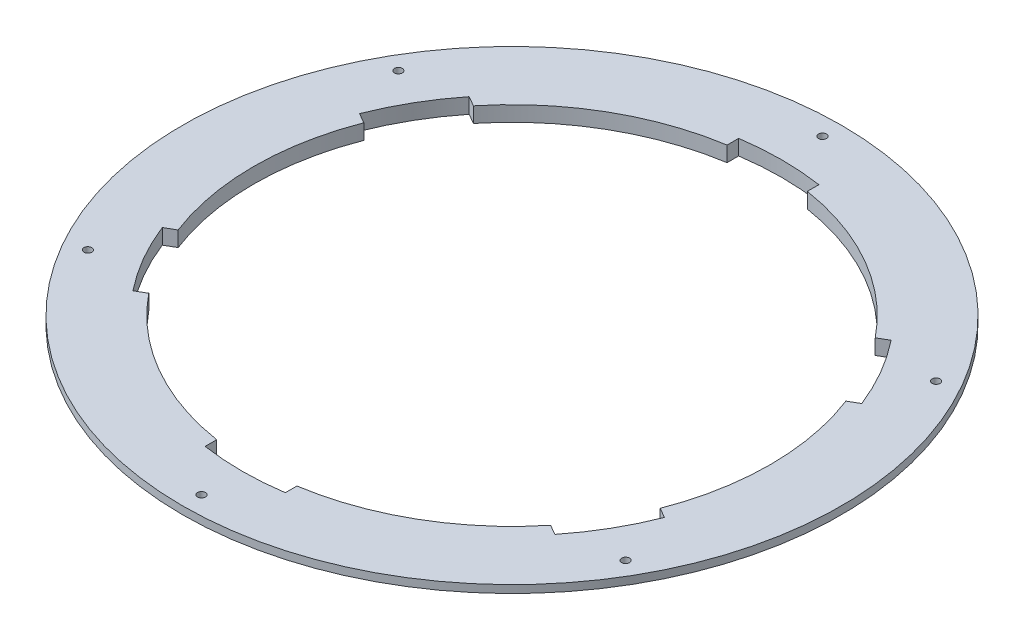
SolidWorks part; units mm, degrees
ref_plane "Front Plane" through (0, 0, 0) normal (0, 0, 1) x (1, 0, 0)
ref_plane "Top Plane" through (0, 0, 0) normal (0, 1, 0) x (1, 0, 0)
ref_plane "Right Plane" through (0, 0, 0) normal (1, 0, 0) x (0, 0, -1)
sketch "Sketch1" plane through (0, 0, 0) normal (0, 1, 0) x (1, 0, 0)
  line L0 (-13.335, -84.81) -> (-13.335, -88.6648)
  line L1 (13.335, -84.81) -> (13.335, -88.6648)
  circle A0 centre (0, 0) radius 85.852
  circle A1 centre (0, 0) radius 109.5375
  circle A2 centre (0, 0) radius 89.662
  circle A3 centre (0, -103.1875) radius 1.3208
  dimension "D1" = 171.704
  dimension "D2" = 219.075
  dimension "D8" = 2.6416
  dimension "D4" = 13.335
  dimension "D5" = 13.335
  dimension "D7" = 103.1875
  dimension "D3" = 3.81
extrude "Boss-Extrude1" add sketch "Sketch1" along normal blind 5.08 contours L1 A2 L0 A0 | A1 A2 A0 region at (-15.864, 0, 86.7374) region at (-106.4393, 0, 0)
pattern_circular "CirPattern1" count 6 over 360 about axis through (0, 5.08, 0) along (0, 1, 0) of face at (-13.335, 2.54, 86.7374) of face at (0, 2.54, 89.1634) of face at (13.335, 2.54, 86.7374) of face at (0, 5.08, 104.5083)
sketch "Sketch2" plane through (0, 0, 0) normal (1, 0, 0) x (0, 0, -1)
  line L0 (109.5375, 5.08) -> (-109.5375, 5.08) construction
  line L1 (-109.5375, 0) -> (109.5375, 0) construction
  line L2 (109.5375, 5.08) -> (-109.5375, 5.08)
  line L3 (-109.5375, 0) -> (109.5375, 0)
  line L4 (0, 0) -> (0, 5.08) construction
  circle A0 centre (-108.6231, 0) radius 2.667
  dimension "D1" = 5.334
  dimension "D2" = 0.9144
revolve "Cut-Revolve1" cut sketch "Sketch2" angle 360 about L4 region at (0, 0, 111.2147)
sketch "Sketch4" plane through (0, 0, 0) normal (0, -1, 0) x (1, 0, 0)
  line L0 (0, 0) -> (47.1488, -81.664) construction
  line L1 (0, 0) -> (0, -39.7137) construction
  circle A0 centre (47.1488, -81.664) radius 5.588
  dimension "D2" = 11.176
  dimension "D1" = 94.2975
  dimension "D3" = 30
extrude "Cut-Extrude1" cut sketch "Sketch4" against normal blind 1.905 contours A0 region at (47.1488, 0, -81.664)
pattern_circular "CirPattern2" count 3 over 360 about axis through (0, 0, 0) along (0, 1, 0) of "Cut-Extrude1"
equation "\"Middle Coupler Inner Daimeter\"= 6.25in"
equation "\"Middle Coupler  Wall Thickness\" = 0.25in"
equation "\"Middle Coupler Bottom Thickness\"= 0.2in"
equation "\"Bearing Rail Offset\"= 0.45in"
equation "\"3-56 UNF Tap\"= 0.089in"
equation "\"3-56 UNF Clearance\"= 0.104in"
equation "\"Ball Bearing Distance\"= 0.03in"
equation "\"D1@Sketch1\"=\"Middle Coupler Inner Daimeter\"+0.5+0.005*2in"
equation "\"TCA Outer Diameter\" = 8.625in"
equation "\"D2@Sketch1\"=\"TCA Outer Diameter\""
equation "\"D4@Sketch1\"=0.50 + (0.05/2)"
equation "\"D5@Sketch1\"=\"D4@Sketch1\""
equation "\"D7@Sketch1\"=(\"D2@Sketch1\"-0.5)/2"
equation "\"D8@Sketch1\"=\"3-56 UNF Clearance\""
equation "\"D2@Sketch2\"=\"Interstage Aeroframe Wall Thickness\"/2"
equation "\"Interstage Aeroframe Wall Thickness\" = 0.072in"
equation "\"D1@Sketch4\"=((\"Middle Coupler Inner Daimeter\"+0.625in)/2+\"0.275\")"
equation "\"Compression Spring OD\"= 0.42in"
equation "\"10-24 Tap\"= 0.157in"
equation "\"10-24 Clearance\"= 0.196in"
equation "\"D2@Sketch4\"=\"Compression Spring OD\"+0.02"
equation "\"D3@Sketch1\"=0.125in+(0.05/2)"
